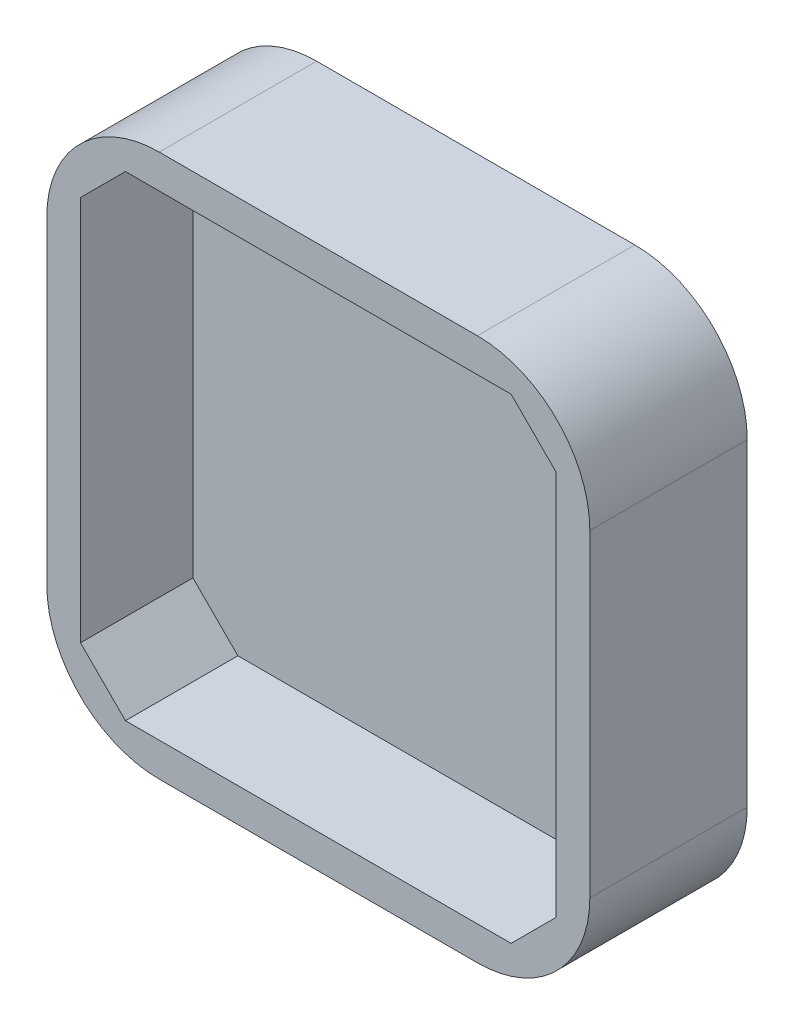
SolidWorks part; units mm, degrees
ref_plane "Front Plane" through (0, 0, 0) normal (0, 0, 1) x (1, 0, 0)
ref_plane "Top Plane" through (0, 0, 0) normal (0, 1, 0) x (1, 0, 0)
ref_plane "Right Plane" through (0, 0, 0) normal (1, 0, 0) x (0, 0, -1)
sketch "Sketch1" plane through (0, 0, 7.6139) normal (0, 0, -1) x (-1, 0, 0)
  line L0 (106.8836, -12.7052) -> (72.5836, -12.7052) construction
  line L1 (113.8836, -15.7052) -> (65.5836, -15.7052)
  line L2 (113.8836, -15.7052) -> (113.8836, 32.5948)
  line L3 (113.8836, 32.5948) -> (65.5836, 32.5948)
  line L4 (65.5836, -15.7052) -> (65.5836, 32.5948)
  line L5 (113.8836, -15.7052) -> (65.5836, 32.5948) construction
  line L6 (113.8836, 32.5948) -> (65.5836, -15.7052) construction
  line L7 (110.8836, -8.7052) -> (106.8836, -12.7052)
  line L8 (110.8836, 25.5948) -> (110.8836, -8.7052) construction
  line L9 (72.5836, 29.5948) -> (106.8836, 29.5948) construction
  line L10 (106.8836, -12.7052) -> (72.5836, -12.7052)
  line L11 (110.8836, -8.7052) -> (110.8836, 25.5948)
  line L12 (106.8836, 29.5948) -> (72.5836, 29.5948)
  line L13 (68.5836, -8.7052) -> (68.5836, 25.5948)
  line L14 (110.8836, -12.7052) -> (68.5836, 29.5948) construction
  line L15 (110.8836, 29.5948) -> (68.5836, -12.7052) construction
  line L16 (68.5836, -8.7052) -> (68.5836, 25.5948) construction
  line L17 (106.8836, 29.5948) -> (110.8836, 25.5948)
  line L18 (72.5836, -12.7052) -> (68.5836, -8.7052)
  line L19 (72.5836, 29.5948) -> (68.5836, 25.5948)
  point P0 (89.7336, 8.4448)
  point P10 (89.7336, 8.4448)
  point P36 (105.2336, 23.9448)
  point P37 (105.2336, -7.0552)
  point P39 (74.2336, 23.9448)
  point P41 (74.2336, -7.0552)
  circle M13 centre (74.2336, -7.0552) radius 3.6
  circle M14 centre (105.2336, -7.0552) radius 3.6
  circle M15 centre (105.2336, 23.9448) radius 3.6
  circle M16 centre (74.2336, 23.9448) radius 3.6
  line M17 (106.4694, -11.7052) -> (109.8836, -8.291)
  line M18 (109.8836, -8.291) -> (109.8836, 25.1806)
  line M19 (109.8836, 25.1806) -> (106.4694, 28.5948)
  line M20 (106.4694, 28.5948) -> (72.9978, 28.5948)
  line M21 (72.9978, 28.5948) -> (69.5836, 25.1806)
  line M22 (69.5836, 25.1806) -> (69.5836, -8.291)
  line M23 (69.5836, -8.291) -> (72.9978, -11.7052)
  line M24 (72.9978, -11.7052) -> (106.4694, -11.7052)
  circle M25 centre (89.7336, 8.4448) radius 6.5
  dimension "D1" = 3
  dimension "D2" = 3
extrude "Boss-Extrude1" add sketch "Sketch1" against normal blind 10 contours L4 L1 L2 L3 L19 L12 L17 L11 L7 L10 L18 L13 region at (-89.7336, -15.0221, 7.6139)
extrude "Boss-Extrude2" add sketch "Sketch1<3>" along normal blind 4 contours M24 M17 M18 M19 M20 M21 M22 M23 M14 M16 M25 M15 M13 | L12 L19 L13 L18 L10 L7 L11 L17 M17 M24 M23 M22 M21 M20 M19 M18 | L4 L1 L2 L3 L19 L12 L17 L11 L7 L10 L18 L13 | M15 | M25 | M14 | M13 | M16 region at (-89.7336, -15.0221, 7.6139) region at (-108.4606, -10.2822, 7.6139) region at (-74.2336, -7.0552, 7.6139) region at (-105.2336, -7.0552, 7.6139) region at (-105.2336, 23.9448, 7.6139) region at (-74.2336, 23.9448, 7.6139) region at (-89.7336, -11.1353, 7.6139) region at (-89.7336, 8.4448, 7.6139)
sketch "Sketch1<3>" plane through (0, 0, 7.6139) normal (0, 0, -1) x (-1, 0, 0) same geometry as "Sketch1"
sketch "Sketch2" plane through (0, 0, 3.6139) normal (0, 0, -1) x (-1, 0, 0)
  circle A10 centre (105.2336, 23.9448) radius 1.5
  circle A11 centre (105.2336, -7.0552) radius 1.5
  circle A12 centre (74.2336, -7.0552) radius 1.5
  circle A13 centre (74.2336, 23.9448) radius 1.5
  dimension "D3" = 3
  dimension "D1" = 3
  dimension "D2" = 3
  dimension "D4" = 3
extrude "Cut-Extrude1" cut sketch "Sketch2" against normal blind 3.5
fillet "Fillet1" radius 10 4 edges at (-113.8836, 32.5948, 10.6139) (-113.8836, -15.7052, 10.6139) (-65.5836, -15.7052, 10.6139) (-65.5836, 32.5948, 10.6139)
